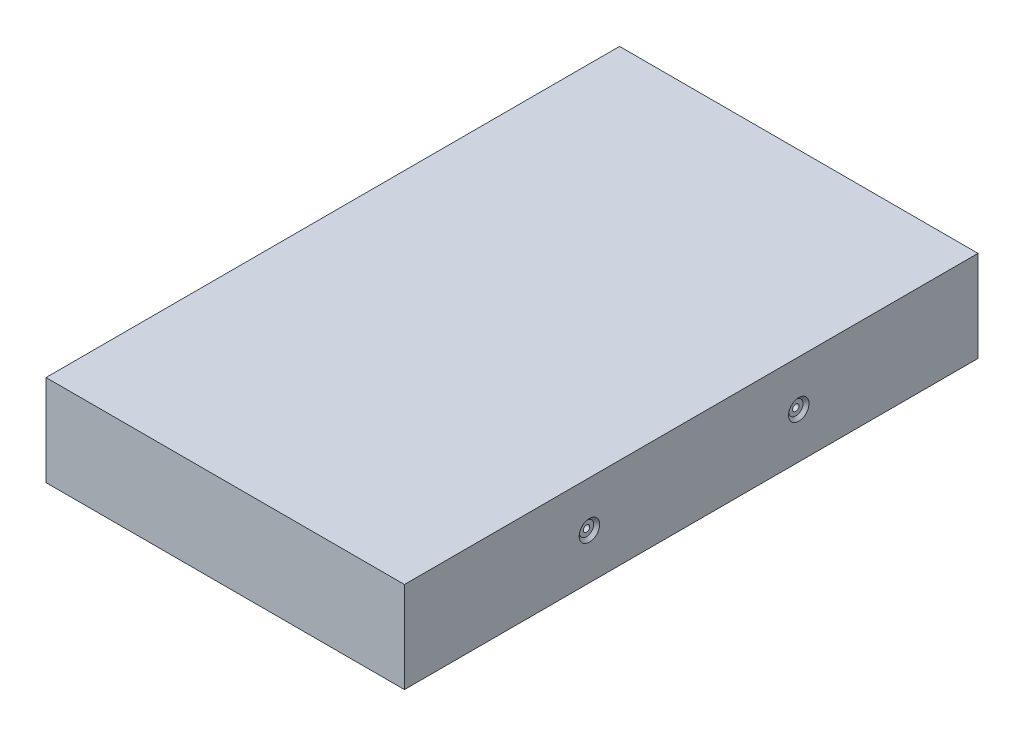
SolidWorks part; units mm, degrees
ref_plane "Front Plane" through (0, 0, 0) normal (0, 0, 1) x (1, 0, 0)
ref_plane "Top Plane" through (0, 0, 0) normal (0, 1, 0) x (1, 0, 0)
ref_plane "Right Plane" through (0, 0, 0) normal (1, 0, 0) x (0, 0, -1)
sketch "Sketch1" plane through (0, 0, 0) normal (0, 1, 0) x (1, 0, 0)
  line L1 (-50, 80) -> (50, 80)
  line L2 (-50, 80) -> (-50, -80)
  line L3 (-50, -80) -> (50, -80)
  line L4 (50, 80) -> (50, -80)
  line L5 (-50, 80) -> (50, -80) construction
  line L6 (-50, -80) -> (50, 80) construction
  point P0 (0, 0)
  dimension "D1" = 100
  dimension "D2" = 160
extrude "Boss-Extrude1" add sketch "Sketch1" along normal blind 25.4
hole_wizard "CBORE for #0 Binding Head Machine Screw1" positions "Sketch2" profile "Sketch3" counterbore size "#0" standard "ANSI Inch"
sketch "Sketch2" plane through (50, 0, 0) normal (1, 0, 0) x (0, 0, -1)
  line L0 (-80, 0) -> (80, 0) construction
  line L2 (80, 25.4) -> (80, 0) construction
  point P0 (-28.4, 12.7)
  point P2 (30, 12.7)
  point P13 (0, 0)
  point P14 (0, 0)
  dimension "D1" = 12.7
  dimension "D2" = 58.4
  dimension "D3" = 50
sketch "Sketch3" plane through (50, 12.7, 28.4) normal (0, 1, 0) x (0, 0, -1)
  line L0 (0, 0) -> (0, 30.5342)
  line L1 (0, 30.5342) -> (0.889, 30)
  line L2 (0.889, 30) -> (0.889, 0.8128)
  line L3 (0.889, 0.8128) -> (1.985, 0.8128)
  line L5 (1.985, 0.8128) -> (1.985, 0.8725)
  line L6 (1.985, 0.8725) -> (2.8575, 0)
  line L7 (2.8575, 0) -> (0, 0)
  line L8 (-1.985, 0.8725) -> (-2.8575, 0) construction
  line L10 (0, 30.5342) -> (-0.889, 30) construction
  line L11 (0, -6.35) -> (0, 107.95) construction
  dimension "Hole Dia." = 1.778
  dimension "Hole Depth" = 30
  dimension "C'Bore Dia." = 3.97
  dimension "C'Bore Depth" = 0.8128
  dimension "Near C'Sink Dia." = 5.715
  dimension "Near C'Sink Angle" = 90
  dimension "Drill Angle" = 118
